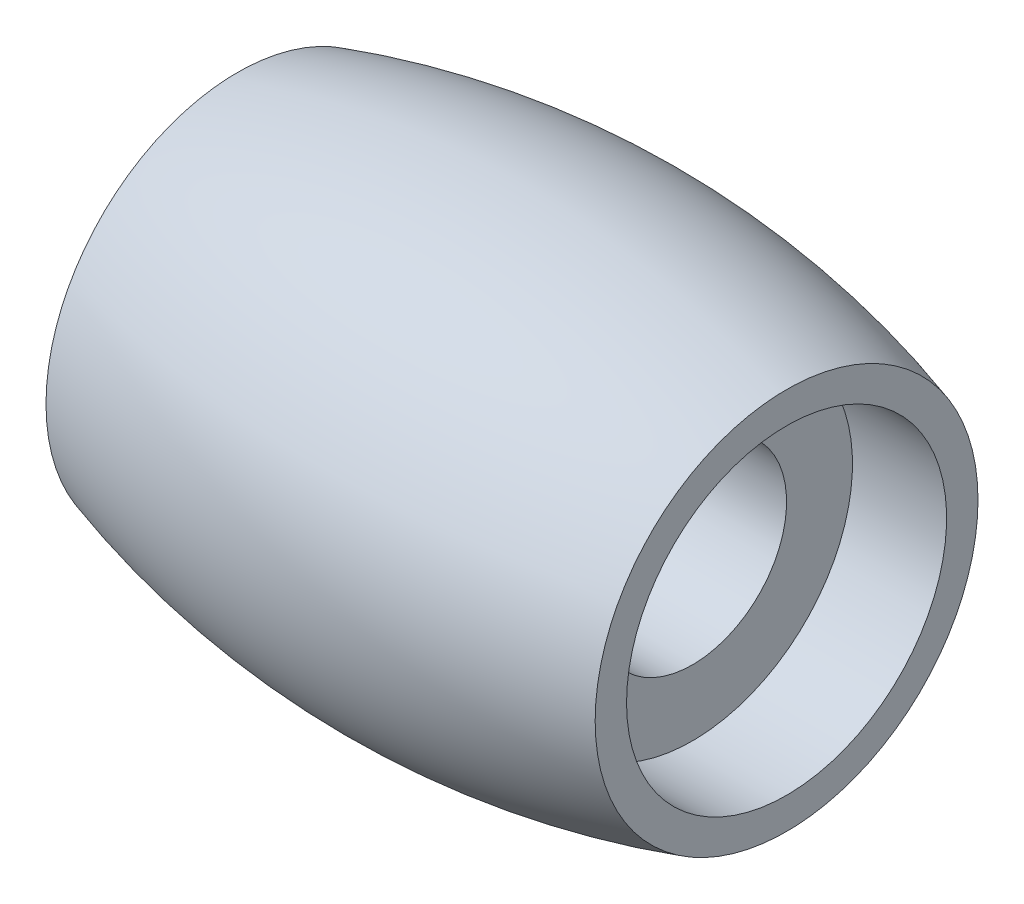
SolidWorks part; units mm, degrees
ref_plane "Front Plane" through (0, 0, 0) normal (0, 0, 1) x (1, 0, 0)
ref_plane "Top Plane" through (0, 0, 0) normal (0, 1, 0) x (1, 0, 0)
ref_plane "Right Plane" through (0, 0, 0) normal (1, 0, 0) x (0, 0, -1)
sketch "Sketch2" plane through (0, 0, 0) normal (0, 0, 1) x (1, 0, 0)
  line L0 (0, 6.5859) -> (0, -8.2148) construction
  line L1 (-8.918, 0) -> (11.5313, 0) construction
  line L2 (-2.875, 1.5) -> (2.875, 1.5)
  line L3 (2.875, 1.5) -> (2.875, 2.55)
  line L4 (2.875, 2.55) -> (4.375, 2.55)
  line L5 (4.375, 2.55) -> (4.375, 3.05)
  line L6 (-4.375, 2.55) -> (-4.375, 3.05)
  line L7 (-2.875, 2.55) -> (-4.375, 2.55)
  line L8 (-2.875, 1.5) -> (-2.875, 2.55)
  arc A0 (-4.375, 3.05) -> (4.375, 3.05) centre (0, -11.2978) cw
  point P18 (0, 1.5)
  dimension "D6" = 15
  dimension "1.5" = 1.5
  dimension "D2" = 1.5
  dimension "2.26" = 2.55
  dimension "D4" = 3.05
  dimension "D5" = 4.375
revolve "Revolve1" add sketch "Sketch2" angle 360 about L1
